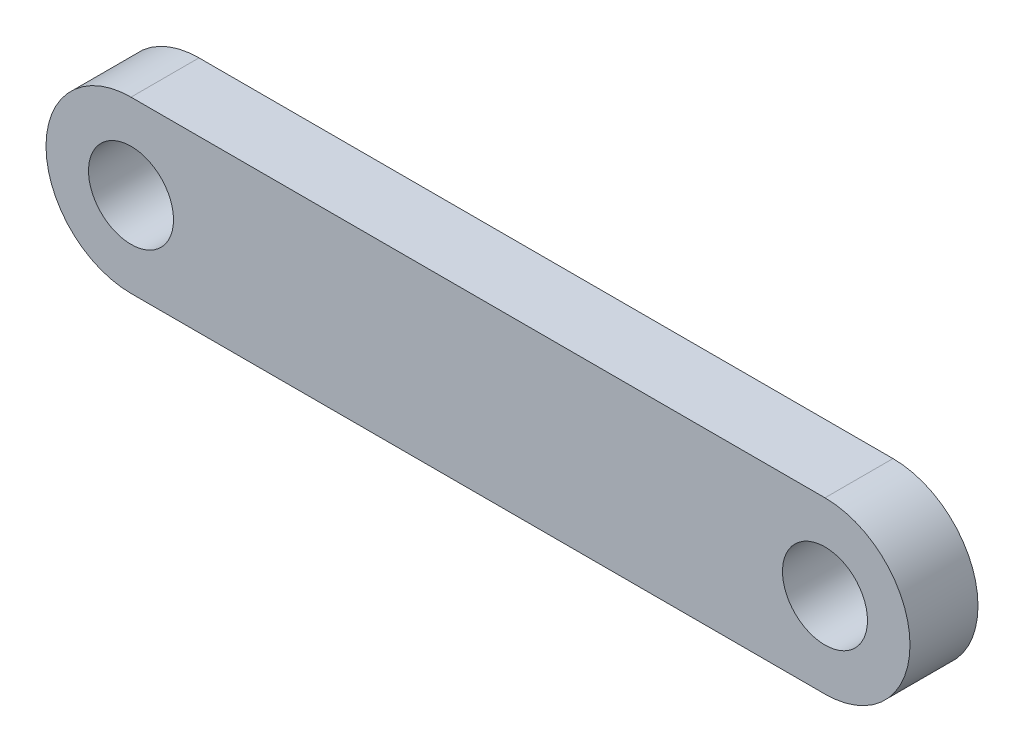
SolidWorks part; units mm, degrees
material "ABS"
ref_plane "Front Plane" through (0, 0, 0) normal (0, 0, 1) x (1, 0, 0)
ref_plane "Top Plane" through (0, 0, 0) normal (0, 1, 0) x (1, 0, 0)
ref_plane "Right Plane" through (0, 0, 0) normal (1, 0, 0) x (0, 0, -1)
sketch "Sketch1" plane through (0, 0, 0) normal (0, 0, 1) x (1, 0, 0)
  line L0 (0, 3.175) -> (25.9207, 3.175)
  line L1 (0, -3.175) -> (25.9207, -3.175)
  circle A0 centre (0, 0) radius 1.5875
  circle A1 centre (0, 0) radius 3.175
  circle A2 centre (25.9207, 0) radius 1.5875
  circle A3 centre (25.9207, 0) radius 3.175
  dimension "D1" = 3.175
  dimension "D2" = 6.35
  dimension "D3" = 25.9207
extrude "Boss-Extrude2" add sketch "Sketch1" along normal blind 2.54 contours A1 A0 | A3 A2 | A3 L0 A1 L1 region at (12.9603, 0, 0) region at (2.1816, 2.1816, 0) region at (28.1023, 2.1816, 0)
